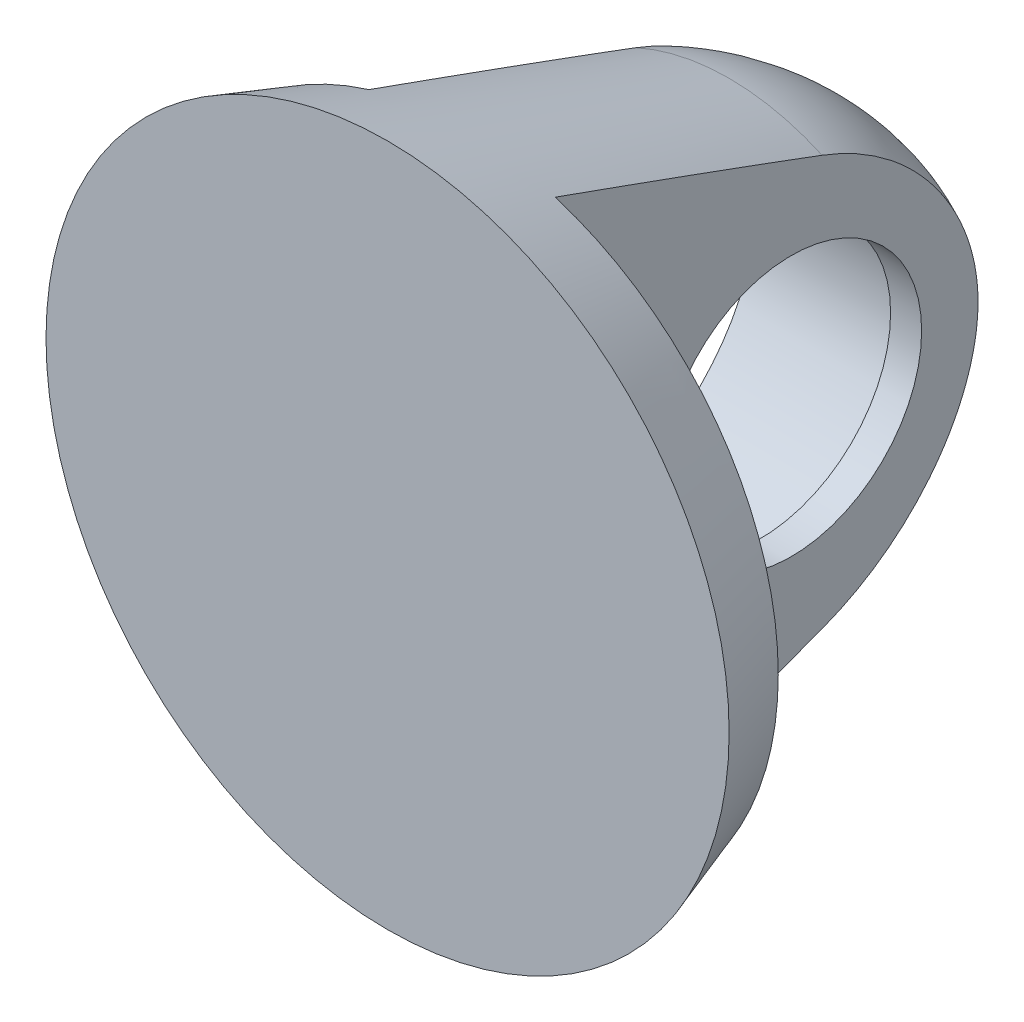
SolidWorks part; units mm, degrees
ref_plane "Front Plane" through (0, 0, 0) normal (0, 0, 1) x (1, 0, 0)
ref_plane "Top Plane" through (0, 0, 0) normal (0, 1, 0) x (1, 0, 0)
ref_plane "Right Plane" through (0, 0, 0) normal (1, 0, 0) x (0, 0, -1)
sketch "Sketch1" plane through (0, 0, 0) normal (0, 1, 0) x (1, 0, 0)
  line L0 (0, 0) -> (0, 66455.0104) construction
  line L1 (0, -32.7281) -> (-55, -32.7281)
  line L2 (-55, -32.7281) -> (-36.2609, 22.24)
  line L3 (0, -32.7281) -> (0, 52.2719)
  arc A0 (-36.2609, 22.24) -> (0, 52.2719) centre (6.3321, 7.7196) cw
  dimension "D3" = 45
  dimension "D1" = 85
  dimension "D2" = 55
revolve "Revolve1" add sketch "Sketch1" angle 360 about L0
sketch "Sketch2" plane through (0, 0, 0) normal (0, 1, 0) x (1, 0, 0)
  line L0 (0, -32.7281) -> (0, 49967.2719) construction
  line L1 (-55, -32.7281) -> (55, -32.7281) construction
  line L2 (-50.9898, -20.7281) -> (-15, -20.7281)
  line L3 (-15, -20.7281) -> (-15, 47.3682)
  line L4 (-50.9898, -20.7281) -> (-55, -32.7281)
  line L5 (-55, -32.7281) -> (55, -32.7281)
  line L6 (15, -20.7281) -> (15, 47.3682)
  line L7 (50.9898, -20.7281) -> (15, -20.7281)
  line L8 (50.9898, -20.7281) -> (55, -32.7281)
  arc A0 (0, 52.2719) -> (-36.2609, 22.24) centre (6.3321, 7.7196) ccw construction
  arc A2 (15, 47.3682) -> (0, 52.2719) centre (-6.1863, 7.9547) ccw
  arc A3 (-15, 47.3682) -> (0, 52.2719) centre (6.1863, 7.9547) cw
  point P4 (0, -32.7281)
  point P15 (0, -32.7281)
  dimension "D1" = 12
  dimension "D2" = 30
extrude "Cut-Extrude3" cut sketch "Sketch2" against normal through all both and the other way through all flip side to cut
sketch "Sketch3" plane through (-15, 0, 0) normal (-1, 0, 0) x (0, 0, 1)
  line L0 (32.7281, 0) -> (32.7281, 50000) construction
  line L1 (32.7281, -55) -> (32.7281, 55) construction
  line L2 (20.7281, -48.6491) -> (20.7281, 48.6491) construction
  line L3 (12.7281, -37.2873) -> (12.7281, 37.2873)
  line L5 (19.9355, -39.8714) -> (20.7281, 40.1548)
  line L6 (5.4516, -25.4247) -> (20.0147, -31.8714)
  line L7 (-38.2682, 0.726) -> (-39.3284, 0.7366) construction
  line L8 (5.9644, 25.9998) -> (20.6532, 32.1548)
  circle A0 centre (-17.2692, 0.5167) radius 21
  arc A1 (4.1205, -19.066) -> (4.5067, 19.6689) centre (-17.2692, 0.5167) ccw
  arc A2 (4.1205, -19.066) -> (5.4516, -25.4247) centre (7.0708, -21.7671) ccw
  arc A3 (4.5067, 19.6689) -> (5.9644, 25.9998) centre (7.5103, 22.3106) cw
  spline S9 degree 3 poles (-77.0422, 4777.4678) (1094.885, 259.577) (517.7044, 221.7758) (-408.1258, -116.3776) (-777.408, -360.5565) (404.3201, -4817.5128) knots -48.094261 -48.094261 -48.094261 -48.094261 0.5 0.5 38.246264 38.246264 38.246264 38.246264 only from (12.7281, 37.2873) to (-19.4346, 25.5209)
  spline S10 degree 3 poles (2764.1204, -4115.555) (631.3094, -585.6201) (97.5397, 87.8559) (-24.597, 23.097) (-25.8091, 22.3507) (-27.5582, 21.108) (-28.1318, 20.6717) (-29.2435, 19.7656) (-29.7813, 19.2964) (-31.3419, 17.8413) (-32.312, 16.8081) (-33.6588, 15.1611) (-34.0897, 14.5959) (-34.9136, 13.4314) (-35.3073, 12.8308) (-36.4228, 10.9828) (-37.0681, 9.7096) (-37.8769, 7.7335) (-38.1197, 7.0636) (-38.44, 6.0404) (-38.5393, 5.6962) (-38.7223, 5.0013) (-38.8062, 4.6496) (-39.181, 2.8888) (-39.3388, 1.4716) (-39.3437, -0.6681) (-39.3068, -1.3836) (-39.1556, -2.8193) (-39.0422, -3.5302) (-38.6016, -5.6306) (-38.1748, -6.9943) (-37.3637, -8.9929) (-37.0646, -9.6504) (-36.4217, -10.9289) (-36.077, -11.5528) (-34.9777, -13.3819) (-34.1584, -14.5445) (-32.8056, -16.2071) (-32.3328, -16.749) (-31.3503, -17.7994) (-30.8436, -18.3052) (-29.2786, -19.7666) (-28.1759, -20.6666) (-26.4347, -21.9075) (-25.8397, -22.303) (-24.6202, -23.0569) (-23.9946, -23.4158) (147.8507, -114.6937) (1044.4716, 1333.6297) (2613.9752, 4209.7586) knots -5.948784 -5.948784 -5.948784 -5.948784 0.0625 0.0625 0.125 0.125 0.15625 0.15625 0.1875 0.1875 0.25 0.25 0.28125 0.28125 0.3125 0.3125 0.375 0.375 0.40625 0.40625 0.421875 0.421875 0.4375 0.4375 0.5 0.5 0.53125 0.53125 0.5625 0.5625 0.625 0.625 0.65625 0.65625 0.6875 0.6875 0.75 0.75 0.78125 0.78125 0.8125 0.8125 0.875 0.875 0.90625 0.90625 0.9375 0.9375 9.371778 9.371778 9.371778 9.371778 only from (-19.4346, 25.5209) to (-19.4346, -25.5209)
  spline S11 degree 3 poles (489.3129, 4807.0601) (-778.9289, 361.4255) (-408.7025, 116.5882) (516.4674, -221.324) (1091.5286, -259.1735) (36.7741, -4783.6997) knots -37.300032 -37.300032 -37.300032 -37.300032 0.5 0.5 48.978859 48.978859 48.978859 48.978859 only from (-19.4346, -25.5209) to (12.7281, -37.2873)
  spline S12 degree 3 poles (20.7281, 40.1548) (12.6857, 37.28) (4.6501, 34.3861) (-8.7338, 29.4977) (-14.089, 27.5226) (-19.4346, 25.5209) knots -0.248144 -0.248144 -0.248144 -0.248144 0.5 0.5 1 1 1 1
  spline S13 degree 3 poles (-19.4346, 25.5209) (-20.782, 25.0164) (-22.0834, 24.4297) (-24.597, 23.097) (-25.8091, 22.3507) (-27.5582, 21.108) (-28.1318, 20.6717) (-29.2435, 19.7656) (-29.7813, 19.2964) (-31.3419, 17.8413) (-32.312, 16.8081) (-33.6588, 15.1611) (-34.0897, 14.5959) (-34.9136, 13.4314) (-35.3073, 12.8308) (-36.4228, 10.9828) (-37.0681, 9.7096) (-37.8769, 7.7335) (-38.1197, 7.0636) (-38.44, 6.0404) (-38.5393, 5.6962) (-38.7223, 5.0013) (-38.8062, 4.6496) (-39.181, 2.8888) (-39.3388, 1.4716) (-39.3437, -0.6681) (-39.3068, -1.3836) (-39.1556, -2.8193) (-39.0422, -3.5302) (-38.6016, -5.6306) (-38.1748, -6.9943) (-37.3637, -8.9929) (-37.0646, -9.6504) (-36.4217, -10.9289) (-36.077, -11.5528) (-34.9777, -13.3819) (-34.1584, -14.5445) (-32.8056, -16.2071) (-32.3328, -16.749) (-31.3503, -17.7994) (-30.8436, -18.3052) (-29.2786, -19.7666) (-28.1759, -20.6666) (-26.4347, -21.9075) (-25.8397, -22.303) (-24.6202, -23.0569) (-23.9946, -23.4158) (-22.0915, -24.4267) (-20.7829, -25.016) (-19.4346, -25.5209) knots 0 0 0 0 0.0625 0.0625 0.125 0.125 0.15625 0.15625 0.1875 0.1875 0.25 0.25 0.28125 0.28125 0.3125 0.3125 0.375 0.375 0.40625 0.40625 0.421875 0.421875 0.4375 0.4375 0.5 0.5 0.53125 0.53125 0.5625 0.5625 0.625 0.625 0.65625 0.65625 0.6875 0.6875 0.75 0.75 0.78125 0.78125 0.8125 0.8125 0.875 0.875 0.90625 0.90625 0.9375 0.9375 1 1 1 1
  spline S14 degree 3 poles (-19.4346, -25.5209) (-14.0891, -27.5225) (-8.7337, -29.4977) (4.3866, -34.2898) (12.1577, -37.0898) (19.9355, -39.8714) knots 0 0 0 0 0.5 0.5 1.223564 1.223564 1.223564 1.223564
  point P14 (32.7281, 0)
  point P24 (20.3318, 0.1417)
  point P28 (-0.1958, -22.9247)
  point P31 (0.2683, 23.6129)
  dimension "D2" = 42
  dimension "D4" = 29
  dimension "D7" = 4
  dimension "D3" = 50
  dimension "D5" = 8
  dimension "D6" = 8
  dimension "D1" = 8
extrude "Cut-Extrude8" cut sketch "Sketch3" against normal through all both contours A0
sketch "Sketch7" plane through (0, 0, 0) normal (1, 0, 0) x (0, 0, -1)
  line L0 (-4.0859, 28.1899) -> (-17.8643, 33.2544)
  line L2 (-17.764, 41.2185) -> (-18.806, -41.5913)
  line L3 (-14.7281, 40.1306) -> (-14.7281, -40.1306)
  line L5 (-3.5218, -27.5537) -> (-18.7053, -33.5913)
  arc A0 (-2.3006, -20.8848) -> (-3.5218, -27.5537) centre (-4.9998, -23.8368) cw
  arc A1 (-2.7102, 21.5363) -> (-2.3006, -20.8848) centre (17.2692, 0.5167) ccw
  arc A2 (-4.0859, 28.1899) -> (-2.7102, 21.5363) centre (-5.4659, 24.4355) cw
  spline S9 degree 3 poles (-266.4933, -3795.071) (-1036.2399, -263.0599) (-492.6953, -214.4836) (377.1207, 102.7077) (722.8173, 317.8123) (-192.3426, 3843.9749) knots -42.120857 -42.120857 -42.120857 -42.120857 0.5 0.5 32.709078 32.709078 32.709078 32.709078 only from (-14.7281, -40.1306) to (20.1359, -27.3939)
  spline S10 degree 3 poles (-2270.6832, 3240.2876) (-544.9501, 459.5899) (-88.529, -85.5233) (25.6595, -24.7952) (26.9547, -23.9945) (28.8222, -22.6611) (29.434, -22.1932) (30.6235, -21.2179) (31.1985, -20.713) (32.8656, -19.1474) (33.9, -18.0363) (35.8115, -15.6761) (36.6892, -14.4272) (38.2691, -11.777) (38.9522, -10.4089) (39.8055, -8.2879) (40.0612, -7.5694) (40.5098, -6.107) (40.7029, -5.3613) (41.1748, -3.0933) (41.3387, -1.5744) (41.3438, 0.7147) (41.3054, 1.4796) (41.1877, 2.6296) (41.1382, 3.0141) (41.0208, 3.7759) (40.9527, 4.1541) (40.568, 6.0323) (40.1197, 7.4942) (39.2661, 9.6349) (38.9497, 10.3421) (38.2679, 11.7183) (37.9021, 12.3895) (36.7349, 14.3562) (35.8643, 15.6048) (34.4267, 17.3889) (33.9254, 17.9687) (32.8783, 19.0981) (32.3354, 19.6444) (30.6628, 21.2178) (29.4846, 22.1851) (27.6252, 23.5172) (26.99, 23.9414) (25.6885, 24.7495) (25.0206, 25.1342) (-144.7862, 115.6289) (-970.4793, -1218.913) (-2149.3233, -3319.7529) knots -5.185281 -5.185281 -5.185281 -5.185281 0.0625 0.0625 0.125 0.125 0.15625 0.15625 0.1875 0.1875 0.25 0.25 0.3125 0.3125 0.375 0.375 0.40625 0.40625 0.4375 0.4375 0.5 0.5 0.53125 0.53125 0.546875 0.546875 0.5625 0.5625 0.625 0.625 0.65625 0.65625 0.6875 0.6875 0.75 0.75 0.78125 0.78125 0.8125 0.8125 0.875 0.875 0.90625 0.90625 0.9375 0.9375 8.713804 8.713804 8.713804 8.713804 only from (20.1359, -27.3939) to (20.1359, 27.3939)
  spline S11 degree 3 poles (-203.2825, -3842.9826) (723.072, -317.9506) (377.2167, -102.7427) (-492.632, 214.4605) (-1036.0823, 263.04) (-269.9883, 3794.982) knots -31.717353 -31.717353 -31.717353 -31.717353 0.5 0.5 43.115422 43.115422 43.115422 43.115422 only from (20.1359, 27.3939) to (-14.7281, 40.1306)
  spline S12 degree 3 poles (-18.806, -41.5913) (-11.6215, -39.0216) (-4.443, -36.4351) (8.5374, -31.7016) (14.3424, -29.5633) (20.1359, -27.3939) knots -0.116697 -0.116697 -0.116697 -0.116697 0.5 0.5 1 1 1 1
  spline S13 degree 3 poles (20.1359, -27.3939) (21.5789, -26.8536) (22.9716, -26.2247) (25.6595, -24.7952) (26.9547, -23.9945) (28.8222, -22.6611) (29.434, -22.1932) (30.6235, -21.2179) (31.1985, -20.713) (32.8656, -19.1474) (33.9, -18.0363) (35.8115, -15.6761) (36.6892, -14.4272) (38.2691, -11.777) (38.9522, -10.4089) (39.8055, -8.2879) (40.0612, -7.5694) (40.5098, -6.107) (40.7029, -5.3613) (41.1748, -3.0933) (41.3387, -1.5744) (41.3438, 0.7147) (41.3054, 1.4796) (41.1877, 2.6296) (41.1382, 3.0141) (41.0208, 3.7759) (40.9527, 4.1541) (40.568, 6.0323) (40.1197, 7.4942) (39.2661, 9.6349) (38.9497, 10.3421) (38.2679, 11.7183) (37.9021, 12.3895) (36.7349, 14.3562) (35.8643, 15.6048) (34.4267, 17.3889) (33.9254, 17.9687) (32.8783, 19.0981) (32.3354, 19.6444) (30.6628, 21.2178) (29.4846, 22.1851) (27.6252, 23.5172) (26.99, 23.9414) (25.6885, 24.7495) (25.0206, 25.1342) (22.9816, 26.2208) (21.5799, 26.8532) (20.1359, 27.3939) knots 0 0 0 0 0.0625 0.0625 0.125 0.125 0.15625 0.15625 0.1875 0.1875 0.25 0.25 0.3125 0.3125 0.375 0.375 0.40625 0.40625 0.4375 0.4375 0.5 0.5 0.53125 0.53125 0.546875 0.546875 0.5625 0.5625 0.625 0.625 0.65625 0.65625 0.6875 0.6875 0.75 0.75 0.78125 0.78125 0.8125 0.8125 0.875 0.875 0.90625 0.90625 0.9375 0.9375 1 1 1 1
  spline S14 degree 3 poles (20.1359, 27.3939) (14.3424, 29.5633) (8.5374, 31.7016) (-4.0965, 36.3088) (-10.9275, 38.7714) (-17.764, 41.2185) knots 0 0 0 0 0.5 0.5 1.086884 1.086884 1.086884 1.086884
  point P3 (-28.7926, 37.3138)
  point P9 (0, 0)
  point P14 (-18.285, -0.1864)
  point P15 (0, 0)
  point P16 (2.9512, -25.705)
  dimension "D2" = 29
  dimension "D4" = 4
  dimension "D3" = 8
  dimension "D5" = 8
  dimension "D1" = 6
extrude "Cut-Extrude14" cut sketch "Sketch7" against normal through all from offset 10 contours S13 S14 L2 L0 A2 A1 A0 L5 S12 region at (0, 0.072, -13.9386) region at (0, 33.1274, 4.4202) region at (0, 36.6544, 16.2703) region at (0, -33.0822, 4.4856) region at (0, -36.8454, 16.7353)
